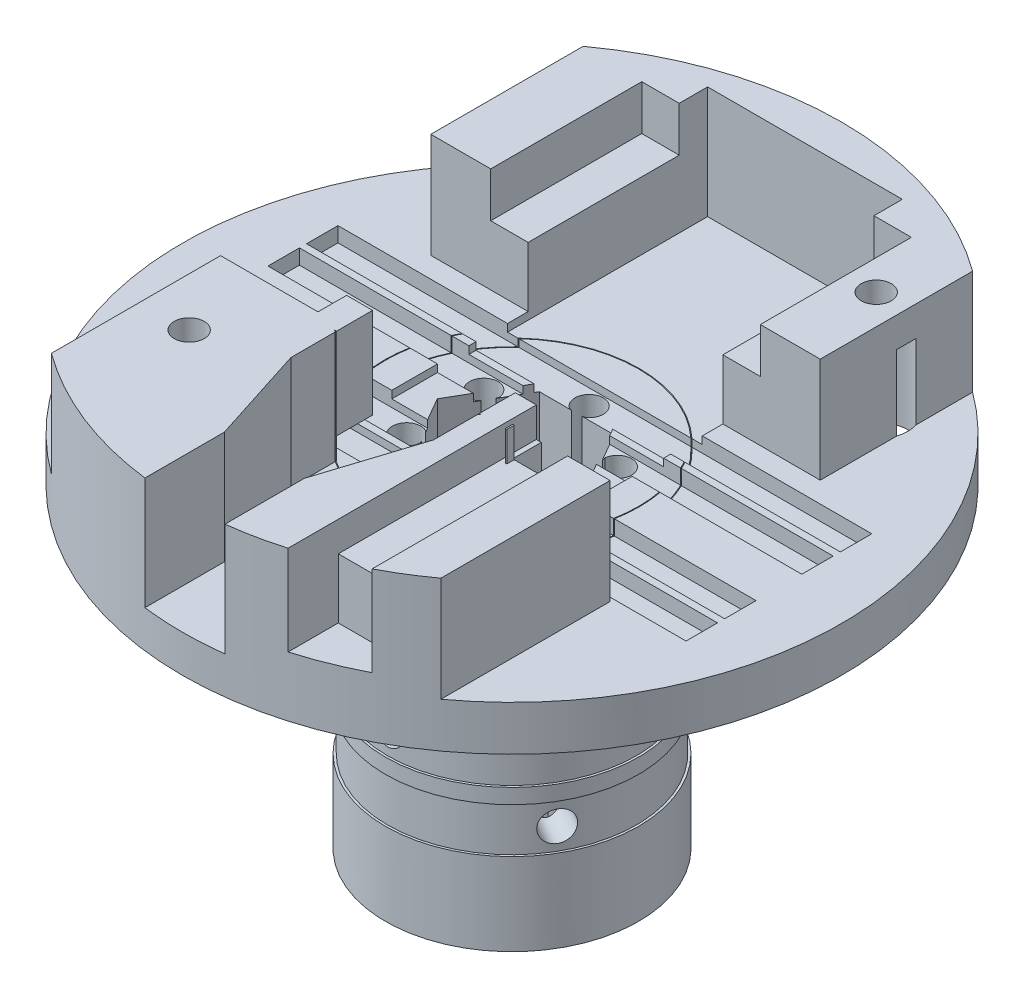
SolidWorks part; units mm, degrees
ref_plane "Front Plane" through (0, 0, 0) normal (0, 0, 1) x (1, 0, 0)
ref_plane "Top Plane" through (0, 0, 0) normal (0, 1, 0) x (1, 0, 0)
ref_plane "Right Plane" through (0, 0, 0) normal (1, 0, 0) x (0, 0, -1)
sketch "Sketch1" plane through (0, 0, 0) normal (0, 1, 0) x (1, 0, 0)
  circle A0 centre (0, 0) radius 22
extrude "Boss-Extrude1" add sketch "Sketch1" along normal blind 8 and the other way blind 2
sketch "Sketch2" plane through (0, 8, 0) normal (0, 1, 0) x (1, 0, 0)
  line L0 (0, 0) -> (0, -22) construction
  circle A0 centre (0, 0) radius 22 construction
ref_plane "Plane4" through (0, -2, 0) normal (0, -1, 0) x (-1, 0, 0)
sketch "Sketch6" plane through (0, -2, 0) normal (0, -1, 0) x (-1, 0, 0)
  circle A0 centre (0, 0) radius 21
  circle A1 centre (0, 0) radius 12.5
extrude "Cut-Extrude5" cut sketch "Sketch6" against normal blind 1
sketch "Sketch7" plane through (0, -2, 0) normal (0, -1, 0) x (-1, 0, 0)
  circle A0 centre (0, 0) radius 8.5
extrude "Boss-Extrude2" add sketch "Sketch7" along normal blind 21 contours A0
sketch "Sketch8" plane through (0, -2, 0) normal (0, -1, 0) x (-1, 0, 0)
  circle A0 centre (0, 0) radius 1.5
extrude "Cut-Extrude6" cut sketch "Sketch8" against normal through all and the other way through all contours A0
sketch "Sketch9" plane through (0, 8, 0) normal (0, 1, 0) x (1, 0, 0)
  line L0 (0, 0) -> (-13.0007, 0) construction
  line L1 (-13.0007, -20.3592) -> (-13.0007, 20.3592)
  line L2 (13, -20.3597) -> (13, 20.3597)
  line L3 (0, 0) -> (13, 0) construction
  arc A0 (13, -20.3597) -> (13, 20.3597) centre (0, 0) ccw
  arc A1 (-13.0007, 20.3592) -> (-13.0007, -20.3592) centre (0, 0) ccw
extrude "Cut-Extrude7" cut sketch "Sketch9" against normal blind 7
ref_plane "Plane5" through (0, -23, 0) normal (0, -1, 0) x (-1, 0, 0)
sketch "Sketch17" plane through (0, -23, 0) normal (0, -1, 0) x (-1, 0, 0)
  line L0 (3.5101, 2.5625) -> (2.4943, 4.3215)
  line L1 (-4.9897, -0.0006) -> (-3.9745, -1.7585)
  line L2 (-2.4943, -4.3215) -> (-0.4644, -4.3212)
  line L3 (2.4953, -4.3209) -> (3.5101, -2.5628)
  line L4 (4.9897, 0.0006) -> (3.9745, 1.7585)
  line L5 (2.4943, 4.3215) -> (0.4644, 4.3212)
  line L6 (-2.4953, 4.3209) -> (-3.5101, 2.5628)
  line L7 (-0.4642, 4.3211) -> (-2.4953, 4.3209)
  line L8 (-3.9743, 1.7586) -> (-4.9897, -0.0006)
  line L9 (-3.5101, -2.5625) -> (-2.4943, -4.3215)
  line L10 (0.4642, -4.3211) -> (2.4953, -4.3209)
  line L11 (3.9743, -1.7586) -> (4.9897, 0.0006)
  line L12 (3.9743, -1.7586) -> (3.5101, -2.5628) construction
  line L13 (4.9917, -0.0006) -> (4.989, -0.0006) construction
  line L14 (3.9743, -1.7586) -> (3.9243, -1.8452)
  line L15 (3.9243, -1.8452) -> (4.0897, -1.7001)
  line L16 (3.5101, -2.5628) -> (3.5601, -2.4762)
  line L17 (3.5601, -2.4762) -> (3.5173, -2.6919)
  line L18 (0.3642, -4.3211) -> (0.5725, -4.3919)
  line L19 (0.4642, -4.3211) -> (0.3642, -4.3211)
  line L20 (-0.3644, -4.3212) -> (-0.5727, -4.392)
  line L21 (-0.4644, -4.3212) -> (-0.3644, -4.3212)
  line L22 (-3.5601, -2.4759) -> (-3.5172, -2.6917)
  line L23 (-3.5101, -2.5625) -> (-3.5601, -2.4759)
  line L24 (-3.9245, -1.8451) -> (-4.0899, -1.7001)
  line L25 (-3.9745, -1.7585) -> (-3.9245, -1.8451)
  line L26 (-3.9243, 1.8452) -> (-4.0897, 1.7001)
  line L27 (-3.9743, 1.7586) -> (-3.9243, 1.8452)
  line L28 (-3.5601, 2.4762) -> (-3.5173, 2.6919)
  line L29 (-3.5101, 2.5628) -> (-3.5601, 2.4762)
  line L30 (-0.3642, 4.3211) -> (-0.5725, 4.3919)
  line L31 (-0.4642, 4.3211) -> (-0.3642, 4.3211)
  line L32 (0.3644, 4.3212) -> (0.5727, 4.392)
  line L33 (0.4644, 4.3212) -> (0.3644, 4.3212)
  line L34 (3.5601, 2.4759) -> (3.5172, 2.6917)
  line L35 (3.5101, 2.5625) -> (3.5601, 2.4759)
  line L36 (3.9245, 1.8451) -> (4.0899, 1.7001)
  line L37 (3.9745, 1.7585) -> (3.9245, 1.8451)
  arc A2 (0.5727, 4.392) -> (-0.5725, 4.3919) centre (0, 5.15) ccw
  arc A3 (4.0899, 1.7001) -> (3.5172, 2.6917) centre (4.46, 2.575) ccw
  arc A4 (3.5173, -2.6919) -> (4.0897, -1.7001) centre (4.46, -2.575) ccw
  arc A5 (-0.5727, -4.392) -> (0.5725, -4.3919) centre (0, -5.15) ccw
  arc A6 (-4.0899, -1.7001) -> (-3.5172, -2.6917) centre (-4.46, -2.575) ccw
  arc A7 (-3.5173, 2.6919) -> (-4.0897, 1.7001) centre (-4.46, 2.575) ccw
  point P11 (-0.4642, 4.3211)
  point P24 (0, 0)
  point P65 (0, 0)
  dimension "D1" = 6
  dimension "D2" = 6
extrude "Cut-Extrude14" cut sketch "Sketch17" against normal blind 62
ref_plane "Plane6" through (0, 8, 0) normal (0, 1, 0) x (1, 0, 0)
sketch "Sketch18" plane through (0, 8, 0) normal (0, 1, 0) x (1, 0, 0)
  line L0 (0, -22.0336) -> (0, 23.1421) construction
sketch "Sketch23" plane through (0, 8, 0) normal (0, 1, 0) x (1, 0, 0)
  line L0 (-2.6704, -16.8582) -> (-2.6704, -16.5304)
  line L1 (6.5, 19.5569) -> (6.5, -6.9431)
  line L2 (-6.5, 19.5569) -> (-6.5, -6.9431)
  line L3 (0, -25.25) -> (0, 0) construction
  line L4 (2.6704, -16.8582) -> (2.6704, -16.5304)
  line L5 (4.7624, -10) -> (2.5704, -16.8425) construction
  line L6 (-4.7624, -10) -> (-2.5704, -16.8425) construction
  line L7 (-4.7624, -10) -> (-2.6704, -16.5304)
  line L8 (0, -25.25) -> (-1.0006, -21.9772)
  line L9 (-6.5, 19.5569) -> (6.5, 19.5569)
  line L10 (-6.5, -6.9431) -> (-4.7624, -6.9431)
  line L11 (6.5, -6.9431) -> (4.7624, -6.9431)
  line L12 (-2.6704, -16.8582) -> (-2.6704, -21.9381) construction
  line L13 (2.6704, -16.8582) -> (2.6704, -21.9381) construction
  line L15 (1.0006, -21.9772) -> (0, -25.25)
  line L16 (4.7624, -10) -> (2.6704, -16.5304)
  line L17 (-2.6704, -16.8582) -> (-2.6704, -21.8373)
  line L19 (-4.7624, -10) -> (-4.7624, -6.9431)
  line L21 (4.7624, -10) -> (4.7624, -6.9431)
  line L22 (2.6704, -16.8582) -> (2.6704, -21.8373)
  line L32 (0, -25.592) -> (-1.0756, -22.0738) construction
  line L33 (1.0756, -22.0738) -> (0, -25.592) construction
  line L34 (4.8624, -10.0156) -> (2.6704, -16.8582) construction
  line L35 (4.8624, -10.0156) -> (4.8624, -7.0431) construction
  line L36 (6.6, -7.0431) -> (4.8624, -7.0431) construction
  line L37 (6.6, 19.6569) -> (6.6, -7.0431) construction
  line L38 (-6.6, 19.6569) -> (6.6, 19.6569) construction
  line L39 (-6.6, 19.6569) -> (-6.6, -7.0431) construction
  line L40 (-6.6, -7.0431) -> (-4.8624, -7.0431) construction
  line L41 (-4.8624, -10.0156) -> (-4.8624, -7.0431) construction
  line L42 (-4.8624, -10.0156) -> (-2.6704, -16.8582) construction
  line L43 (2.5704, -16.8425) -> (2.5704, -21.8493) construction
  line L44 (-2.5704, -16.8425) -> (-2.5704, -21.8493) construction
  arc A0 (-2.6704, -21.8373) -> (-1.0006, -21.9772) centre (0, 0) ccw
  arc A1 (1.0006, -21.9772) -> (2.6704, -21.8373) centre (0, 0) ccw
  arc A4 (1.0756, -22.0738) -> (2.6704, -21.9381) centre (0, 0) ccw construction
  arc A5 (-2.6704, -21.9381) -> (-1.0756, -22.0738) centre (0, 0) ccw construction
  arc A6 (-2.5704, -21.8493) -> (-1.0006, -21.9772) centre (0, 0) ccw construction
  arc A7 (1.0006, -21.9772) -> (2.5704, -21.8493) centre (0, 0) ccw construction
  dimension "D1" = 180
ref_plane "Plane10" through (0, 0, 6.4558) normal (0, 0, -1) x (-1, 0, 0)
sketch "Sketch29" plane through (0, 8, 0) normal (0, 1, 0) x (1, 0, 0)
  line L0 (9, 17.6622) -> (9, -6.4558)
  line L1 (9, 17.6622) -> (-9, 17.6622)
  line L2 (9, -6.4558) -> (-9, -6.4558)
  line L3 (0, -6.4558) -> (0, 17.6622) construction
  line L4 (-9, -6.4558) -> (-9, 17.6622)
  point P5 (0, -6.4558)
  point P8 (0, 17.6622)
extrude "Cut-Extrude19" cut sketch "Sketch29" against normal blind 3
sketch "Sketch30" plane through (0, 8, 0) normal (0, 1, 0) x (1, 0, 0)
  line L0 (-8.0021, 17.6622) -> (-8.0021, -6.4558) construction
  line L1 (8.0021, -6.4558) -> (5.5021, -6.4558)
  line L2 (8.0021, -6.4558) -> (8.0021, 7.5442)
  line L3 (8.0021, 7.5442) -> (5.5021, 7.5442)
  line L4 (-8.0021, -6.4558) -> (-8.0021, 7.5442)
  line L5 (5.5021, 7.5442) -> (5.5021, -6.4558)
  line L8 (-5.5021, 7.5442) -> (-5.5021, -6.4558)
  line L9 (-5.5021, 7.5442) -> (-8.0021, 7.5442)
  line L10 (-5.5021, -6.4558) -> (-8.0021, -6.4558)
  point P7 (5.5021, 7.5442)
  dimension "D1" = 2.5
extrude "Cut-Extrude20" cut sketch "Sketch30" against normal blind 6
ref_plane "Plane11" through (0, 3, 0) normal (0, -1, 0) x (-1, 0, 0)
sketch "Sketch32" plane through (0, 3, 0) normal (0, -1, 0) x (-1, 0, 0)
  circle A1 centre (-5.1962, -3) radius 0.85
  circle A3 centre (5.1962, -3) radius 0.85
  circle A5 centre (5.1962, 3) radius 0.85
  circle A6 centre (-5.1962, 3) radius 0.85
  circle A7 centre (0, 6) radius 0.0479
  circle A8 centre (0, 6) radius 0.85
  circle A9 centre (0, -6) radius 0.85
extrude "Cut-Extrude22" [suppressed] cut sketch "Sketch32" against normal blind 11 and the other way through all
ref_plane "Plane12" through (0, 2, 0) normal (0, 1, 0) x (1, 0, 0)
sketch "Sketch33" [suppressed] plane through (0, 2, 0) normal (0, 1, 0) x (1, 0, 0)
  circle A0 centre (5.1962, 3) radius 1.1
  circle A1 centre (5.1962, -3) radius 1.1
  circle A2 centre (-5.1962, 3) radius 1.1
  circle A3 centre (-5.1962, -3) radius 1.1
  circle A4 centre (0, -6) radius 1.1
  circle A5 centre (0, 6) radius 1.1
extrude "Cut-Extrude23" [suppressed] cut sketch "Sketch33" against normal blind 2 and the other way through all
ref_plane "Plane13" through (0, 2, 0) normal (0, 1, 0) x (1, 0, 0)
sketch "Sketch34" plane through (0, 2, 0) normal (0, 1, 0) x (1, 0, 0)
  line L0 (-1.3341, 5.3583) -> (7.9939, 5.3583)
  line L1 (-7.985, 6.6083) -> (-1.2507, 6.6083)
  line L2 (-7.985, 6.6083) -> (-7.985, 5.3583)
  line L3 (-7.985, 5.3583) -> (-1.3341, 5.3583)
  line L4 (7.9939, 6.6083) -> (7.9939, 5.3583)
  line L5 (-1.2507, 6.6083) -> (7.9939, 6.6083)
  line L6 (8.0021, -6.4558) -> (-8.0021, -6.4558)
  line L7 (-8.0021, -6.4558) -> (-8.0021, -5.2058)
  line L8 (-8.0021, 7.5442) -> (-8.0021, -6.4558) construction
  line L9 (-8.0021, -5.2058) -> (8.0021, -5.2058)
  line L10 (8.0021, -5.2058) -> (8.0021, -6.4558)
extrude "Cut-Extrude27" [suppressed] cut sketch "Sketch34" against normal blind 2
ref_plane "Plane14" through (0, -6.5, 0) normal (0, 1, 0) x (1, 0, 0)
ref_plane "Plane15" through (0, -12, 0) normal (0, 1, 0) x (1, 0, 0)
sketch "Sketch36" plane through (0, -12, 0) normal (0, 1, 0) x (1, 0, 0)
  circle A0 centre (0, 0) radius 8.3
  circle A1 centre (0, 0) radius 8.5
extrude "Cut-Extrude28" cut sketch "Sketch36" against normal blind 1.5 and the other way blind 1.5
ref_plane "Plane16" through (0, -16, 0) normal (0, 1, 0) x (1, 0, 0)
ref_plane "Plane20" through (0, -37, 0) normal (0, 1, 0) x (1, 0, 0)
sketch "Sketch39" plane through (0, -16, 0) normal (0, 1, 0) x (1, 0, 0)
  circle A0 centre (0, 0) radius 8.3
  circle A1 centre (0, 0) radius 8.5
extrude "Cut-Extrude30" cut sketch "Sketch39" against normal blind 1.5 and the other way blind 1.5
sketch "Sketch44" plane through (0, 0, 0) normal (0, 0, 1) x (1, 0, 0)
  line L0 (0, 0) -> (0, -11.9724) construction
  line L1 (0, -11.9724) -> (0, -29.0422) construction
  circle A0 centre (0, -11.9724) radius 1
  point P4 (0, -11.9724)
extrude "Cut-Extrude35" cut sketch "Sketch44" against normal through all and the other way through all
ref_axis "Axis1" through (0, -23, 0) along (0, 1, 0)
ref_plane "Plane21" through (0, 0, 0) normal (0.866, 0, 0.5) x (0, 1, 0)
sketch "Sketch45" plane through (0, 0, 0) normal (0.866, 0, 0.5) x (0, 1, 0)
  line L0 (0, 0) -> (-16.0471, 0) construction
  line L1 (-16.0471, 0) -> (-33.0495, 0) construction
  circle A0 centre (-16.0471, 0) radius 1
  point P4 (-16.0471, 0)
extrude "Cut-Extrude36" cut sketch "Sketch45" against normal through all and the other way through all
ref_plane "Plane22" through (0, 0, 0) normal (0.866, 0, -0.5) x (0, 1, 0)
ref_plane "Plane23" through (0, 8, 0) normal (0, 1, 0) x (1, 0, 0)
sketch "Sketch47" plane through (0, 8, 0) normal (0, 1, 0) x (1, 0, 0)
  line L1 (13.8544, -6.4558) -> (-13.8777, -6.4558)
  line L2 (13.8544, -6.4558) -> (13.8544, 7.5778)
  line L3 (13.8544, 7.5778) -> (-13.8777, 7.5778)
  line L4 (-13.8777, -6.4558) -> (-13.8777, 7.5778)
extrude "Cut-Extrude38" cut sketch "Sketch47" against normal blind 7
extrude "Cut-Extrude39" cut sketch "Sketch23" against normal blind 7.5
sketch "Sketch48" plane through (0, 8, 0) normal (0, 1, 0) x (1, 0, 0)
  line L0 (0, 0) -> (0, 34.87) construction
  line L1 (11, 7.5778) -> (11, 19.0526) construction
  line L2 (13, 7.5778) -> (9, 7.5778) construction
  line L3 (11, 19.0526) -> (11, 13.3152) construction
  line L4 (11, 13.3152) -> (0, 0) construction
  line L5 (0, 0) -> (-17.1456, -20.7543) construction
  line L6 (-9.7504, -6.4558) -> (-9.7504, -16.5924) construction
  line L7 (-13.0007, -6.4558) -> (-6.5, -6.4558) construction
  arc A0 (13, 17.7482) -> (-13.0007, 17.7477) centre (0, 0) ccw construction
  circle A1 centre (11, 13.3152) radius 1
  circle A2 centre (-9.7504, -11.8025) radius 1
  dimension "D1" = 39.561
extrude "Cut-Extrude40" cut sketch "Sketch48" against normal blind 9
sketch "Sketch49" plane through (0, -1, 0) normal (0, -1, 0) x (1, 0, 0)
  circle A0 centre (-9.7504, 11.8025) radius 2.1
  circle A1 centre (11, -13.3152) radius 2.1
sketch "Sketch50" plane through (0, -23, 0) normal (0, -1, 0) x (1, 0, 0)
  line L0 (4.9897, 0.0006) -> (-4.9897, -0.0006) construction
  line L2 (-4.9897, -0.0006) -> (-2.4943, -4.3215)
  line L3 (-2.4943, -4.3215) -> (2.4953, -4.3209)
  line L4 (2.4953, -4.3209) -> (4.9897, 0.0006)
  line L5 (4.9897, 0.0006) -> (2.4943, 4.3215)
  line L6 (2.4943, 4.3215) -> (-2.4953, 4.3209)
  line L7 (-2.4953, 4.3209) -> (-4.9897, -0.0006)
  circle A0 centre (0, 0) radius 4.3212 construction
  circle A1 centre (0, 0) radius 6.3883
extrude "Boss-Extrude5" add sketch "Sketch50" against normal blind 2
sketch "Sketch51" plane through (0, 1, 0) normal (0, 1, 0) x (1, 0, 0)
  line L1 (-4.46, 2.575) -> (4.46, 2.575) construction
  line L3 (-17.8187, 4.1) -> (17.8187, 4.1)
  line L4 (-17.8187, 4.1) -> (-17.8187, 6.2)
  line L5 (-17.8187, 6.2) -> (17.8187, 6.2)
  line L6 (17.8187, 4.1) -> (17.8187, 6.2)
  line L7 (-17.8187, 4.1) -> (17.8187, 6.2) construction
  line L8 (-17.8187, 6.2) -> (17.8187, 4.1) construction
  line L9 (-4.46, -2.575) -> (4.46, -2.575) construction
  line L10 (-17.8187, 3.625) -> (17.8187, 3.625)
  line L11 (-17.8187, 3.625) -> (-17.8187, 1.525)
  line L12 (-17.8187, 1.525) -> (17.8187, 1.525)
  line L13 (17.8187, 3.625) -> (17.8187, 1.525)
  line L14 (-17.8187, 3.625) -> (17.8187, 1.525) construction
  line L15 (-17.8187, 1.525) -> (17.8187, 3.625) construction
  line L17 (-17.8187, -3.625) -> (17.8187, -3.625)
  line L18 (-17.8187, -3.625) -> (-17.8187, -1.525)
  line L19 (-17.8187, -1.525) -> (17.8187, -1.525)
  line L20 (17.8187, -3.625) -> (17.8187, -1.525)
  line L21 (-17.8187, -3.625) -> (17.8187, -1.525) construction
  line L22 (-17.8187, -1.525) -> (17.8187, -3.625) construction
  line L23 (-17.8187, -6.2) -> (17.8187, -6.2)
  line L24 (-17.8187, -6.2) -> (-17.8187, -4.1)
  line L25 (-17.8187, -4.1) -> (17.8187, -4.1)
  line L26 (17.8187, -6.2) -> (17.8187, -4.1)
  line L27 (-17.8187, -6.2) -> (17.8187, -4.1) construction
  line L28 (-17.8187, -4.1) -> (17.8187, -6.2) construction
  point P0 (0, 5.15)
  point P7 (0, 2.575)
  point P14 (0, -2.575)
  point P22 (0, -5.15)
extrude "Cut-Extrude42" cut sketch "Sketch49" against normal blind 7
extrude "Cut-Extrude43" cut sketch "Sketch51" against normal blind 1
sketch "Sketch52" plane through (0, 8, 0) normal (0, 1, 0) x (1, 0, 0)
  line L0 (4.7624, -6.9431) -> (4.7624, -20.5361) construction
  line L1 (4.7624, -17.7644) -> (8.1673, -17.7644) construction
  line L2 (6.1673, -17.7644) -> (10.1673, -17.7644)
  line L3 (6.1673, -17.7644) -> (6.1673, -6.9431)
  line L4 (4.7624, -6.9431) -> (6.6, -6.9431) construction
  line L5 (10.1673, -17.7644) -> (10.1673, -6.4558)
  line L6 (55, -6.4558) -> (-55, -6.4558) construction
  line L7 (10.1673, -6.4558) -> (6.6, -6.4558)
  line L8 (6.6, -6.4558) -> (6.6, -6.2) construction
  line L9 (6.6, -6.4558) -> (6.6, -6.9431)
  line L10 (6.6, -6.9431) -> (6.1673, -6.9431)
  point P8 (8.1673, -17.7644)
extrude "Cut-Extrude44" cut sketch "Sketch52" against normal blind 2
sketch "Sketch53" plane through (0, -23, 0) normal (0, -1, 0) x (1, 0, 0)
  circle A0 centre (0, 0) radius 8.5
  circle A1 centre (0, 0) radius 8.45
extrude "Cut-Extrude45" cut sketch "Sketch53" against normal blind 33.5
sketch "Sketch54" plane through (0, 8, 0) normal (0, 1, 0) x (1, 0, 0)
  line L0 (10.1673, -17.7644) -> (10.1673, -19.5096)
  line L1 (6.1673, -17.7644) -> (6.1673, -21.1179)
  line L2 (6.1673, -21.1179) -> (6.1673, -17.7644)
  arc A0 (6.1673, -21.1179) -> (10.1673, -19.5096) centre (0, 0) ccw
  line M2 (10.1673, -17.7644) -> (6.1673, -17.7644)
  arc M8 (2.6704, -21.8373) -> (13, -17.7482) centre (0, 0) ccw
extrude "Cut-Extrude46" cut sketch "Sketch54" against normal blind 6 contours L1 L0 M2 M8 region at (7.9636, 8, 19.1182)
sketch "Sketch55" plane through (0, 0, 6.9431) normal (0, 0, -1) x (-1, 0, 0)
  line L0 (-4.7624, 8) -> (-6.1673, 8)
  line L1 (-6.1673, 8) -> (-6.1673, 6)
  line L2 (-6.1673, 6) -> (-6.5, 6)
  line L3 (-6.5, 6) -> (-6.5, 1.9457)
  line L4 (-6.5, 1.9457) -> (-4.7624, 1.9457)
  line L5 (-4.7624, 1.9457) -> (-4.7624, 8)
  line L6 (6.5, 8) -> (4.7624, 8)
  line L7 (4.7624, 8) -> (4.7624, 1.9457)
  line L8 (4.7624, 0.5) -> (4.7624, 8) construction
  line L9 (4.7624, 1.9457) -> (6.5, 1.9457)
  line L10 (6.5, 0.5) -> (6.5, 8) construction
  line L11 (6.5, 1.9457) -> (6.5, 8)
extrude "Boss-Extrude6" add sketch "Sketch55" along normal blind 2.4
